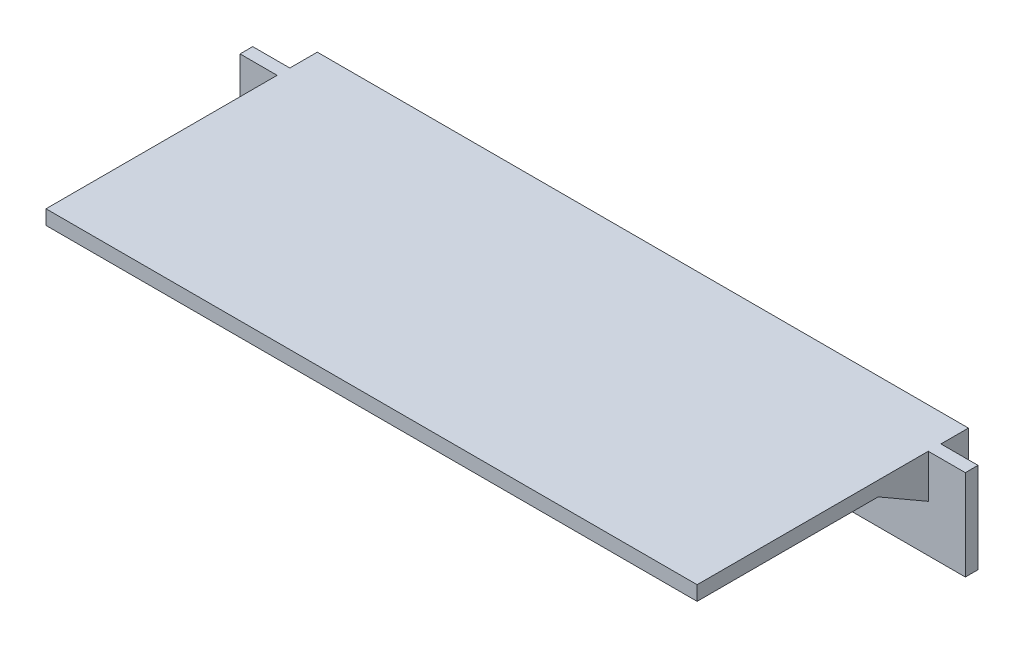
SolidWorks part; units mm, degrees
ref_plane "Front Plane" through (0, 0, 0) normal (0, 0, 1) x (1, 0, 0)
ref_plane "Top Plane" through (0, 0, 0) normal (0, 1, 0) x (1, 0, 0)
ref_plane "Right Plane" through (0, 0, 0) normal (1, 0, 0) x (0, 0, -1)
sketch "Sketch1" plane through (0, 0, 0) normal (0, 1, 0) x (1, 0, 0)
  line L1 (100.25, -1.75) -> (-100.25, -1.75)
  line L2 (100.25, -1.75) -> (100.25, 1.75)
  line L3 (100.25, 1.75) -> (-100.25, 1.75)
  line L4 (-100.25, -1.75) -> (-100.25, 1.75)
  line L5 (100.25, -1.75) -> (-100.25, 1.75) construction
  line L6 (100.25, 1.75) -> (-100.25, -1.75) construction
  point P0 (0, 0)
  dimension "D1" = 200.5
  dimension "D2" = 3.5
extrude "Boss-Extrude1" add sketch "Sketch1" along normal blind 21
sketch "Sketch3" plane through (0, 21, 0) normal (0, 1, 0) x (1, 0, 0)
  line L3 (-90, 9.35) -> (90, 9.35)
  line L4 (90, -65.65) -> (90, 9.35)
  line L6 (-90, 9.35) -> (-90, -65.65)
  line L7 (-90, -65.65) -> (90, -65.65)
  line L8 (100.25, -1.75) -> (90, -1.75) construction
  line L9 (-100.25, -1.75) -> (100.25, -1.75) construction
  line L10 (-90, -1.75) -> (-100.25, -1.75) construction
  line L11 (100.25, 1.75) -> (-100.25, 1.75) construction
  dimension "D1" = 7.6
  dimension "D2" = 10.25
  dimension "D3" = 75
extrude "Boss-Extrude2" add sketch "Sketch3" along normal blind 4
chamfer "Chamfer1" distance 8 angle 60 2 edges at (0, 21, -1.75) (0, 21, 1.75) first distance on face at (0, 14, -1.75) first distance on face at (0, 14, 1.75)
sketch "Sketch4" plane through (0, 21, 0) normal (0, 1, 0) x (1, 0, 0)
  line L0 (-90, -1.75) -> (-90, 1.75) construction
  line L1 (-90, 1.75) -> (-100.25, 1.75) construction
  line L2 (-100.25, 1.75) -> (-100.25, -1.75) construction
  line L3 (-100.25, -1.75) -> (-90, -1.75) construction
  line L4 (90, 1.75) -> (90, -1.75) construction
  line L5 (90, -1.75) -> (100.25, -1.75) construction
  line L6 (100.25, -1.75) -> (100.25, 1.75) construction
  line L7 (100.25, 1.75) -> (90, 1.75) construction
  line L8 (-90, -1.75) -> (-90, 1.75)
  line L9 (-90, 1.75) -> (-100.25, 1.75)
  line L10 (-100.25, 1.75) -> (-100.25, -1.75)
  line L11 (-100.25, -1.75) -> (-90, -1.75)
  line L12 (90, 1.75) -> (90, -1.75)
  line L13 (90, -1.75) -> (100.25, -1.75)
  line L14 (100.25, -1.75) -> (100.25, 1.75)
  line L15 (100.25, 1.75) -> (90, 1.75)
extrude "Boss-Extrude3" add sketch "Sketch4" along normal up to surface (4 mm away) up to face at (0, 25, 28.15)
